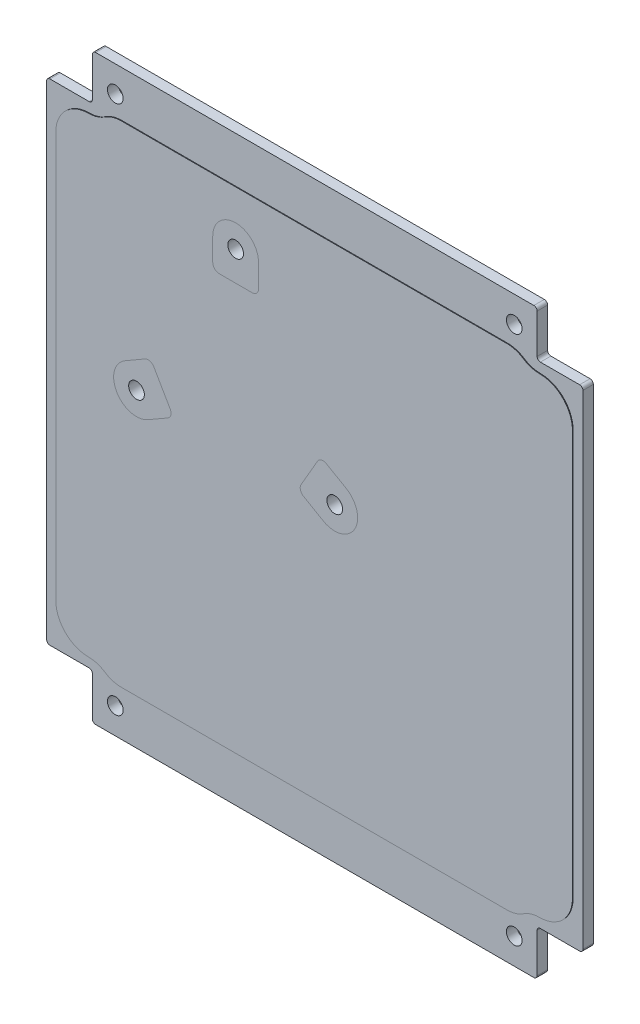
SolidWorks part; units mm, degrees
material "PET"
ref_plane "Front Plane" through (0, 0, 0) normal (0, 0, 1) x (1, 0, 0)
ref_plane "Top Plane" through (0, 0, 0) normal (0, 1, 0) x (1, 0, 0)
ref_plane "Right Plane" through (0, 0, 0) normal (1, 0, 0) x (0, 0, -1)
sketch "Sketch1" plane through (0, 0, 0) normal (0, 0, 1) x (1, 0, 0)
  line L0 (-34, 44) -> (-34, 38)
  line L1 (-33.5, -44.5) -> (33.5, -44.5)
  line L2 (-41, 37) -> (-41, -37)
  line L3 (-33.5, 44.5) -> (33.5, 44.5)
  line L4 (41, -37) -> (41, 37)
  line L5 (34, -44) -> (34, -38)
  line L6 (34.5, -37.5) -> (40.5, -37.5)
  line L7 (-34.5, 37.5) -> (-40.5, 37.5)
  line L8 (34, 44) -> (34, 38)
  line L9 (34.5, 37.5) -> (40.5, 37.5)
  line L10 (-40.5, -37.5) -> (-34.5, -37.5)
  line L11 (-34, -38) -> (-34, -44)
  line L12 (-34.5, -38) -> (34.5, 38) construction
  line L13 (34.5, -38) -> (-34.5, 38) construction
  arc A0 (-33.5, 44.5) -> (-34, 44) centre (-33.5, 44) ccw
  arc A1 (33.5, 44.5) -> (34, 44) centre (33.5, 44) cw
  arc A2 (34, 38) -> (34.5, 37.5) centre (34.5, 38) ccw
  arc A3 (40.5, 37.5) -> (41, 37) centre (40.5, 37) cw
  arc A4 (33.5, -44.5) -> (34, -44) centre (33.5, -44) ccw
  arc A5 (34.5, -37.5) -> (34, -38) centre (34.5, -38) ccw
  arc A6 (40.5, -37.5) -> (41, -37) centre (40.5, -37) ccw
  arc A7 (-34, -44) -> (-33.5, -44.5) centre (-33.5, -44) ccw
  arc A8 (-34, -38) -> (-34.5, -37.5) centre (-34.5, -38) ccw
  arc A9 (-41, -37) -> (-40.5, -37.5) centre (-40.5, -37) ccw
  arc A10 (-40.5, 37.5) -> (-41, 37) centre (-40.5, 37) ccw
  arc A11 (-34.5, 37.5) -> (-34, 38) centre (-34.5, 38) ccw
  point P0 (0, 0)
  dimension "D4" = 0.5
  dimension "D1" = 7
  dimension "D2" = 7
  dimension "D3" = 7
  dimension "D5" = 7
  dimension "D6" = 7
  dimension "D7" = 7
  dimension "D8" = 7
  dimension "D9" = 7
  dimension "D10" = 89
  dimension "D11" = 82
extrude "Boss-Extrude1" add sketch "Sketch1" along normal blind 1.6
sketch "Esboço1" plane through (0, 0, 1.6) normal (0, 0, 1) x (1, 0, 0)
  line L0 (11.8117, 0) -> (-11.978, 0) construction
  line L1 (-29.5, -37.5) -> (29.5, -37.5)
  line L2 (0, 10.1561) -> (0, -5.0161) construction
  line L3 (-29.5, 37.5) -> (29.5, 37.5)
  line L5 (-29.5, -32.5) -> (29.5, 32.5) construction
  line L6 (-29.5, 32.5) -> (29.5, -32.5) construction
  line L8 (-39.5, -31) -> (-39.5, 31)
  line L10 (39.5, -31) -> (39.5, 31)
  line L11 (-39.5, -36) -> (39.5, 36) construction
  line L12 (-39.5, 36) -> (39.5, -36) construction
  arc A0 (-34.5, 36) -> (-32, 36.75) centre (-34.5, 40.5417) ccw
  arc A1 (-29.5, 37.5) -> (-32, 36.75) centre (-29.5, 32.9583) ccw
  arc A2 (-29.5, -37.5) -> (-32, -36.75) centre (-29.5, -32.9583) cw
  arc A3 (-34.5, -36) -> (-32, -36.75) centre (-34.5, -40.5417) cw
  arc A4 (34.5, 36) -> (39.5, 31) centre (34.5, 31) cw
  arc A5 (34.5, -36) -> (39.5, -31) centre (34.5, -31) ccw
  arc A6 (-34.5, -36) -> (-39.5, -31) centre (-34.5, -31) cw
  arc A7 (-39.5, 31) -> (-34.5, 36) centre (-34.5, 31) cw
  arc A8 (29.5, -37.5) -> (32, -36.75) centre (29.5, -32.9583) ccw
  arc A9 (34.5, -36) -> (32, -36.75) centre (34.5, -40.5417) ccw
  arc A10 (29.5, 37.5) -> (32, 36.75) centre (29.5, 32.9583) cw
  arc A11 (34.5, 36) -> (32, 36.75) centre (34.5, 40.5417) cw
  point P0 (0, 0)
  point P1 (0, 0)
  dimension "D2" = 5
  dimension "D3" = 75
  dimension "D5" = 79
extrude "Boss-Extrude2" add sketch "Esboço1" along normal blind 0.1
hole_wizard "M2 Hole1-FixingStructure" positions "Sketch3" profile "Sketch2" hole size "M2" standard "DIN"
sketch "Sketch3" plane through (0, 0, 0) normal (0, 0, -1) x (-1, 0, 0)
  line L0 (-33.5, 44.5) -> (33.5, 44.5) construction
  line L1 (33.5, -44.5) -> (-33.5, -44.5) construction
  line L2 (-41, -37) -> (-41, 37) construction
  line L3 (41, 37) -> (41, -37) construction
  point P0 (-30.5, 40.5)
  point P2 (30.5, 40.5)
  point P4 (-30.5, -40.5)
  point P6 (30.5, -40.5)
  dimension "D1" = 4
  dimension "D2" = 4
  dimension "D3" = 10.5
  dimension "D4" = 10.5
sketch "Sketch2" plane through (30.5, 40.5, 0) normal (1, 0, 0) x (0, 1, 0)
  line L0 (0, 0) -> (0, 200.721)
  line L1 (0, 200.721) -> (1.2, 200)
  line L2 (1.2, 200) -> (1.2, 0)
  line L5 (1.2, 0) -> (0, 0)
  line L10 (0, 200.721) -> (-1.2, 200) construction
  line L11 (0, -6.35) -> (0, 107.95) construction
  dimension "Hole Dia." = 2.4
  dimension "Hole Depth" = 200
  dimension "Drill Angle" = 118
sketch "Sketch4" plane through (0, 0, 1.7) normal (0, 0, 1) x (1, 0, 0)
  circle A0 centre (-27.1554, 3) radius 1.2 construction
  circle A1 centre (-12, 29.25) radius 1.2 construction
  circle A2 centre (3.1554, 3) radius 1.2 construction
  circle A3 centre (-27.1554, 3) radius 1.2
  circle A4 centre (-12, 29.25) radius 1.2
  circle A5 centre (3.1554, 3) radius 1.2
extrude "Cut-Extrude1" cut sketch "Sketch4" against normal up to surface (1.7 mm away) up to face at (29.3, 40.5, 0)
sketch "Sketch5" plane through (0, 0, 1.7) normal (0, 0, 1) x (1, 0, 0)
  line L5 (-8.5, 29.25) -> (-8.5, 25.75)
  line L6 (-28.9054, 6.0311) -> (-26.7404, 7.2811)
  line L7 (-23.2404, 1.2189) -> (-25.4054, -0.0311)
  line L8 (-28.9054, 6.0311) -> (-25.8744, 7.7811)
  line L9 (-22.3744, 1.7189) -> (-25.4054, -0.0311)
  line L10 (-24.5083, 7.4151) -> (-22.0083, 3.0849)
  line L11 (-24.5083, 7.4151) -> (-22.0083, 3.0849)
  line L12 (-15.5, 25.75) -> (-15.5, 29.25)
  line L13 (-9.5, 24.75) -> (-14.5, 24.75)
  line L14 (1.4054, -0.0311) -> (-1.6256, 1.7189)
  line L15 (1.8744, 7.7811) -> (4.9054, 6.0311)
  line L16 (-1.9917, 3.0849) -> (0.5083, 7.4151)
  circle A0 centre (-12, 11.75) radius 4.1 construction
  arc A3 (-25.8744, 7.7811) -> (-24.5083, 7.4151) centre (-25.3744, 6.9151) cw
  arc A4 (-28.9054, 6.0311) -> (-25.4054, -0.0311) centre (-27.1554, 3) ccw
  arc A5 (-28.9054, 6.0311) -> (-25.4054, -0.0311) centre (-27.1554, 3) ccw
  arc A6 (-22.3744, 1.7189) -> (-22.0083, 3.0849) centre (-22.8744, 2.5849) ccw
  arc A7 (-8.5, 25.75) -> (-9.5, 24.75) centre (-9.5, 25.75) cw
  arc A8 (-8.5, 29.25) -> (-15.5, 29.25) centre (-12, 29.25) ccw
  arc A9 (-15.5, 25.75) -> (-14.5, 24.75) centre (-14.5, 25.75) ccw
  arc A10 (-1.6256, 1.7189) -> (-1.9917, 3.0849) centre (-1.1256, 2.5849) cw
  arc A11 (1.4054, -0.0311) -> (4.9054, 6.0311) centre (3.1554, 3) ccw
  arc A12 (1.8744, 7.7811) -> (0.5083, 7.4151) centre (1.3744, 6.9151) ccw
  point P0 (-12, 11.75)
  point P36 (-12, 11.75)
  dimension "D3" = 1
  dimension "D1" = 1
  dimension "D2" = 1
  dimension "D4" = 3
split line "Split Line1"
